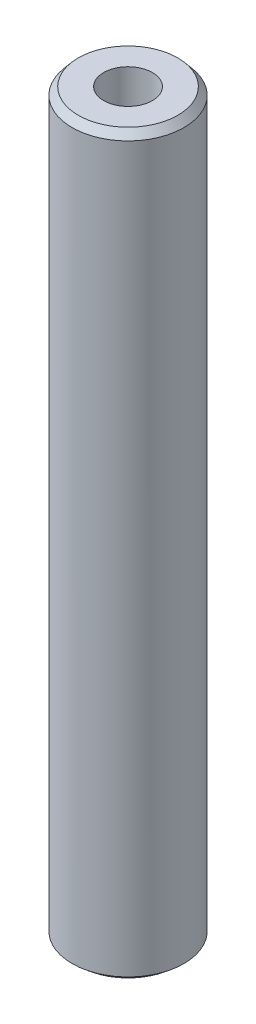
SolidWorks part; units mm, degrees
ref_plane "Front Plane" through (0, 0, 0) normal (0, 0, 1) x (1, 0, 0)
ref_plane "Top Plane" through (0, 0, 0) normal (0, 1, 0) x (1, 0, 0)
ref_plane "Right Plane" through (0, 0, 0) normal (1, 0, 0) x (0, 0, -1)
sketch "Sketch1" plane through (0, 0, 0) normal (0, 1, 0) x (1, 0, 0)
  circle A0 centre (0, 0) radius 25
  dimension "SHAFT_OD" = 50
extrude "Boss-Extrude1" add sketch "Sketch1" along normal blind 329.3907
sketch "Sketch2" plane through (0, 0, 0) normal (0, 1, 0) x (1, 0, 0)
  circle A0 centre (0, 0) radius 10.8715
  dimension "BORE_D" = 21.743
extrude "Cut-Extrude1" cut sketch "Sketch2" along normal through all
chamfer "Chamfer1" distance 3.3505 angle 39.727 2 edges at (0, 329.3907, 25) (0, 0, 25) first distance on face at (0, 329.3907, 25) first distance on face at (0, 0, 10.8715)
